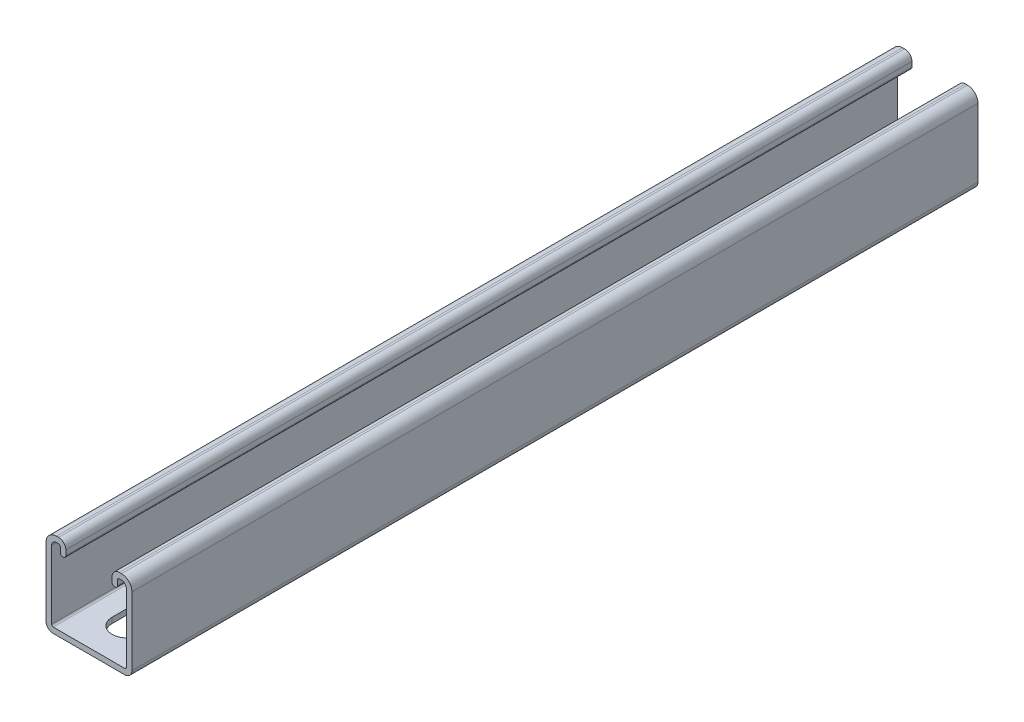
SolidWorks part; units mm, degrees
ref_plane "Front Plane" through (0, 0, 0) normal (0, 0, 1) x (1, 0, 0)
ref_plane "Top Plane" through (0, 0, 0) normal (0, 1, 0) x (1, 0, 0)
ref_plane "Right Plane" through (0, 0, 0) normal (1, 0, 0) x (0, 0, -1)
ref_plane "Plane1" through (0, 0, 3048) normal (0, 0, 1) x (1, 0, 0)
sketch "Sketch1" plane through (0, 0, 0) normal (0, 0, 1) x (1, 0, 0)
  line L0 (-20.6377, 0) -> (-17.9706, 0) construction
  line L1 (20.6377, 0) -> (17.9706, 0) construction
  line L2 (17.1769, -17.9704) -> (-17.1769, -17.9704)
  line L3 (-17.9706, -17.1766) -> (-17.9706, 15.5891)
  line L4 (-15.5894, 17.9704) -> (-14.5734, 17.9704)
  line L5 (-13.7797, 17.1766) -> (-13.7797, 14.8335)
  line L6 (-11.1127, 14.8335) -> (-11.1127, 17.1766)
  line L7 (-14.5734, 20.6374) -> (-15.5894, 20.6374)
  line L8 (-20.6377, 15.5891) -> (-20.6377, -17.1766)
  line L9 (-17.1769, -20.6374) -> (17.1769, -20.6374)
  line L10 (20.6377, 15.5891) -> (20.6377, -17.1766)
  line L11 (14.5734, 20.6374) -> (15.5894, 20.6374)
  line L12 (11.1127, 14.8335) -> (11.1127, 17.1766)
  line L13 (13.7797, 17.1766) -> (13.7797, 14.8335)
  line L14 (0, -17.9704) -> (0, -20.6374) construction
  line L15 (15.5894, 17.9704) -> (14.5734, 17.9704)
  line L16 (17.9706, -17.1766) -> (17.9706, 15.5891)
  arc A0 (-17.1769, -20.6374) -> (-20.6377, -17.1766) centre (-17.1769, -17.1766) cw
  arc A1 (-17.1769, -17.9704) -> (-17.9706, -17.1766) centre (-17.1769, -17.1766) cw
  arc A2 (-17.9706, 15.5891) -> (-15.5894, 17.9704) centre (-15.5894, 15.5891) cw
  arc A3 (-20.6377, 15.5891) -> (-15.5894, 20.6374) centre (-15.5894, 15.5891) cw
  arc A4 (-14.5734, 17.9704) -> (-13.7797, 17.1766) centre (-14.5734, 17.1766) cw
  arc A5 (-14.5734, 20.6374) -> (-11.1127, 17.1766) centre (-14.5734, 17.1766) cw
  arc A6 (-13.7797, 14.8335) -> (-11.1127, 14.8335) centre (-12.4462, 14.8335) ccw
  arc A7 (13.7797, 14.8335) -> (11.1127, 14.8335) centre (12.4462, 14.8335) cw
  arc A8 (14.5734, 20.6374) -> (11.1127, 17.1766) centre (14.5734, 17.1766) ccw
  arc A9 (14.5734, 17.9704) -> (13.7797, 17.1766) centre (14.5734, 17.1766) ccw
  arc A10 (20.6377, 15.5891) -> (15.5894, 20.6374) centre (15.5894, 15.5891) ccw
  arc A11 (17.9706, 15.5891) -> (15.5894, 17.9704) centre (15.5894, 15.5891) ccw
  arc A12 (17.1769, -17.9704) -> (17.9706, -17.1766) centre (17.1769, -17.1766) ccw
  arc A13 (17.1769, -20.6374) -> (20.6377, -17.1766) centre (17.1769, -17.1766) ccw
  dimension "D4" = 3.4608
  dimension "D5" = 5.0483
  dimension "D7" = 3.4608
  dimension "D1" = 34.3538
  dimension "D2" = 41.2748
  dimension "D3" = 2.667
  dimension "D6" = 1.016
  dimension "D8" = 2.3432
extrude "Primary Extrusion" add sketch "Sketch1" against normal blind 406.4
sketch "Sketch58" plane through (0, -20.6374, 0) normal (0, 1, 0) x (-1, 0, 0)
  line L0 (7.1438, -32.5438) -> (7.1438, -18.2562)
  line L1 (-7.1438, -18.2563) -> (-7.1438, -32.5438)
  line L2 (0, 22.7012) -> (0, -22.7012) construction
  line L3 (-7.1438, -25.4) -> (7.1438, -25.4) construction
  line L4 (17.1769, 0) -> (-17.1769, 0) construction
  arc A0 (7.1438, -32.5438) -> (-7.1438, -32.5438) centre (0, -32.5438) cw
  arc A1 (-7.1438, -18.2563) -> (7.1438, -18.2562) centre (0, -18.2563) cw
  dimension "D1" = 14.2875
  dimension "D2" = 14.2875
  dimension "D3" = 25.4
extrude "Slot Cut" cut sketch "Sketch58" along normal up to next contours L0 A1 L1 A0
pattern_linear "LPattern1" count 8 spacing 50.8 along (0, 0, -1) of "Slot Cut"
